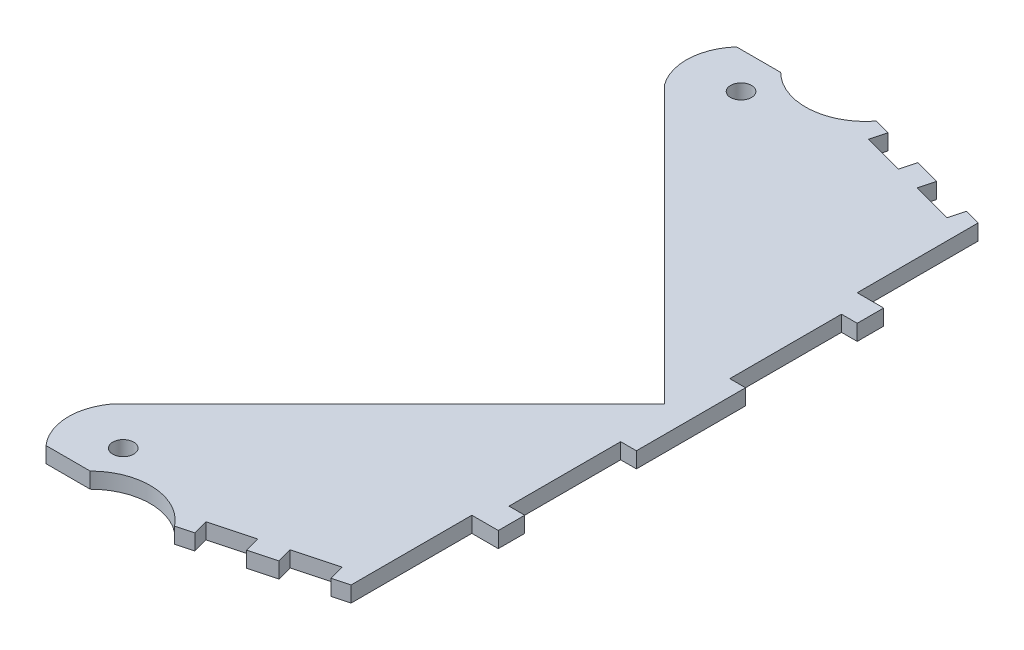
SolidWorks part; units mm, degrees
ref_plane "Front" through (0, 0, 0) normal (0, 0, 1) x (1, 0, 0)
ref_plane "Top" through (0, 0, 0) normal (0, 1, 0) x (1, 0, 0)
ref_plane "Right" through (0, 0, 0) normal (1, 0, 0) x (0, 0, -1)
ref_axis "side-side" through (80.9, 0, 0) along (-1, 0, 0)
ref_axis "up-down" through (0, 50, 0) along (0, -1, 0)
ref_axis "front-back" through (0, 0, -80.9) along (0, 0, 1)
sketch3d "3DSketch1"
  circle A2 centre (-56.825, -4.3, -104.4) radius 5
  arc A3 (-57.4357, -2.0152, -104.4) -> (-55.3111, -2.4831, -104.4) centre (-56.825, -4.3, -104.4) ccw
  circle A7 centre (-56.825, -4.3, 104.9) radius 5.5
  arc A8 (-54.8226, -3.0416, 104.4) -> (-56.6976, -1.9384, 104.4) centre (-56.825, -4.3, 104.4) ccw
  circle A9 centre (-56.825, -4.3, 104.4) radius 5
  point P7 (-56.825, -4.3, -99.4)
  point P8 (-56.825, -4.3, -102.035)
  point P19 (-56.825, -4.3, 110.4)
  point P20 (-56.825, -4.3, 102.035)
  point P22 (-56.825, -4.3, 99.4)
sketch "Sketch1" plane through (0, 0, 0) normal (0, 1, 0) x (1, 0, 0)
  line L0 (-82.6741, 104.4511) -> (-69.3102, 104.4511)
  line L1 (0, 0) -> (-83.6295, 83.6295)
  line L2 (-82.6741, -104.4511) -> (-69.3102, -104.4511)
  line L3 (0, -94.8336) -> (-42.1131, -106.1177)
  line L4 (-42.1131, 106.1177) -> (0, 94.8336)
  line L5 (-70.3102, 110) -> (-56.6019, 110) construction
  line L6 (8, 58.293) -> (8, -58.293)
  line L7 (0, 0) -> (58.8362, 0) construction
  line L8 (-69.3102, 104.4511) -> (-77.0671, 112.2079) construction
  line L10 (0, 0) -> (-83.6295, -83.6295)
  line L12 (0, -94.8336) -> (0, -58.293)
  line L13 (0, -58.293) -> (8, -58.293)
  line L16 (0, 94.8336) -> (0, 58.293)
  line L17 (0, 58.293) -> (8, 58.293)
  circle A0 centre (-70.3102, 93.4511) radius 3.175
  circle A1 centre (-70.3102, -93.4511) radius 3.175
  arc A2 (-83.6295, 83.6295) -> (-82.6741, 104.4511) centre (-70.3102, 93.4511) cw
  arc A3 (-83.6295, -83.6295) -> (-82.6741, -104.4511) centre (-70.3102, -93.4511) ccw
  circle A4 centre (-70.3102, 93.4511) radius 10.6138 construction
  arc A5 (-69.3102, 104.4511) -> (-42.1131, 106.1177) centre (-56.4487, 117.3125) ccw
  arc A6 (-69.3102, -104.4511) -> (-42.1131, -106.1177) centre (-56.4487, -117.3125) cw
  dimension "D5" = 6.35
  dimension "D1" = 21.2276
  dimension "D6" = 11
  dimension "D7" = 16.5489
  dimension "D10" = 64.6019
  dimension "D2" = 110
  dimension "D3" = 8
  dimension "D4" = 45
  dimension "D8" = 15
  dimension "D9" = 1
  dimension "D11" = 75
  dimension "D12" = 116.586
  dimension "D13" = 8
extrude "Boss-Extrude1" add sketch "Sketch1" along normal blind 4.7625
chamfer "Chamfer1" [suppressed] distance 10 distance2 10
sketch "Sketch2" plane through (0, 0, 0) normal (0, 1, 0) x (1, 0, 0)
  line L4 (-17.1928, -99.4404) -> (-4.8296, -96.1276)
  line L5 (-4.8296, -96.1276) -> (-6.0623, -91.5274)
  line L6 (-6.0623, -91.5274) -> (-18.4255, -94.8401)
  line L7 (-18.4255, -94.8401) -> (-17.1928, -99.4404)
  line L8 (-17.1928, -99.4404) -> (-4.8296, -96.1276)
  line L9 (-4.8296, -96.1276) -> (-6.0623, -91.5274)
  line L10 (-6.0623, -91.5274) -> (-18.4255, -94.8401)
  line L11 (-18.4255, -94.8401) -> (-17.1928, -99.4404)
  line L12 (-37.2834, -104.8236) -> (-24.9202, -101.5109)
  line L13 (-24.9202, -101.5109) -> (-26.1529, -96.9107)
  line L14 (-26.1529, -96.9107) -> (-38.5161, -100.2234)
  line L15 (-38.5161, -100.2234) -> (-37.2834, -104.8236)
  line L16 (-37.2834, -104.8236) -> (-24.9202, -101.5109)
  line L17 (-24.9202, -101.5109) -> (-26.1529, -96.9107)
  line L18 (-26.1529, -96.9107) -> (-38.5161, -100.2234)
  line L19 (-38.5161, -100.2234) -> (-37.2834, -104.8236)
  line L20 (3.2375, -50.293) -> (8, -50.293)
  line L21 (8, -50.293) -> (8, -16.51)
  line L22 (8, -16.51) -> (3.2375, -16.51)
  line L23 (3.2375, -16.51) -> (3.2375, -50.293)
  line L24 (3.2375, -50.293) -> (8, -50.293)
  line L25 (8, -50.293) -> (8, -16.51)
  line L26 (8, -16.51) -> (3.2375, -16.51)
  line L27 (3.2375, -16.51) -> (3.2375, -50.293)
  line L28 (-38.5161, 100.2234) -> (-26.1529, 96.9107)
  line L29 (-26.1529, 96.9107) -> (-24.9202, 101.5109)
  line L30 (-24.9202, 101.5109) -> (-37.2834, 104.8236)
  line L31 (-37.2834, 104.8236) -> (-38.5161, 100.2234)
  line L32 (-38.5161, 100.2234) -> (-26.1529, 96.9107)
  line L33 (-26.1529, 96.9107) -> (-24.9202, 101.5109)
  line L34 (-24.9202, 101.5109) -> (-37.2834, 104.8236)
  line L35 (-37.2834, 104.8236) -> (-38.5161, 100.2234)
  line L36 (-18.4255, 94.8401) -> (-6.0623, 91.5274)
  line L37 (-6.0623, 91.5274) -> (-4.8296, 96.1276)
  line L38 (-4.8296, 96.1276) -> (-17.1928, 99.4404)
  line L39 (-17.1928, 99.4404) -> (-18.4255, 94.8401)
  line L40 (-18.4255, 94.8401) -> (-6.0623, 91.5274)
  line L41 (-6.0623, 91.5274) -> (-4.8296, 96.1276)
  line L42 (-4.8296, 96.1276) -> (-17.1928, 99.4404)
  line L43 (-17.1928, 99.4404) -> (-18.4255, 94.8401)
  line L44 (3.2375, 50.293) -> (3.2375, 16.51)
  line L45 (3.2375, 16.51) -> (8, 16.51)
  line L46 (8, 16.51) -> (8, 50.293)
  line L47 (8, 50.293) -> (3.2375, 50.293)
  line L48 (3.2375, 50.293) -> (3.2375, 16.51)
  line L49 (3.2375, 16.51) -> (8, 16.51)
  line L50 (8, 16.51) -> (8, 50.293)
  line L51 (8, 50.293) -> (3.2375, 50.293)
  dimension "D1" = 0
  dimension "D2" = 0
  dimension "D3" = 0
  dimension "D4" = 0
  dimension "D5" = 0
  dimension "D6" = 0
extrude "Cut-Extrude1" cut sketch "Sketch2" along normal blind 5
